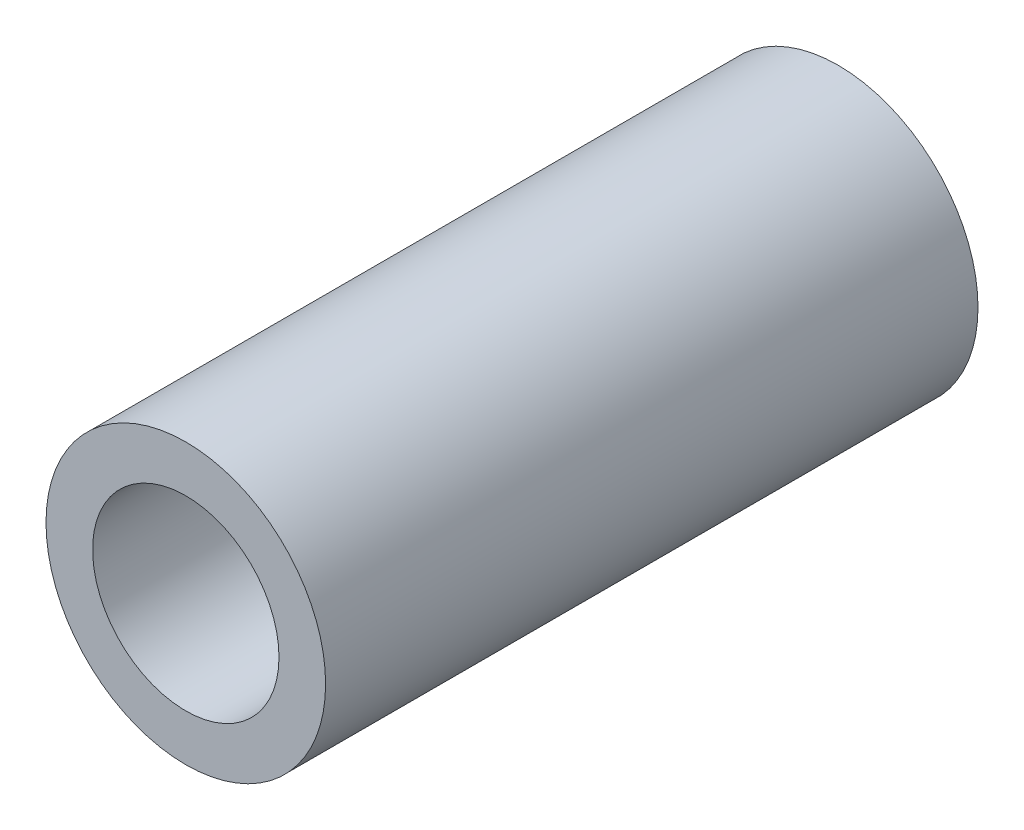
SolidWorks part; units mm, degrees
material "Brass"
ref_plane "Front Plane" through (0, 0, 0) normal (0, 0, 1) x (1, 0, 0)
ref_plane "Top Plane" through (0, 0, 0) normal (0, 1, 0) x (1, 0, 0)
ref_plane "Right Plane" through (0, 0, 0) normal (1, 0, 0) x (0, 0, -1)
sketch "Sketch1" plane through (0, 0, 0) normal (0, 0, 1) x (1, 0, 0)
  circle A0 centre (0, 0) radius 3
  circle A1 centre (0, 0) radius 2
  dimension "D1" = 6
  dimension "D2" = 4
extrude "Boss-Extrude1" add sketch "Sketch1" along normal blind 14
ref_axis "Axis1" through (0, 0, 0) along (0, 0, 1)
